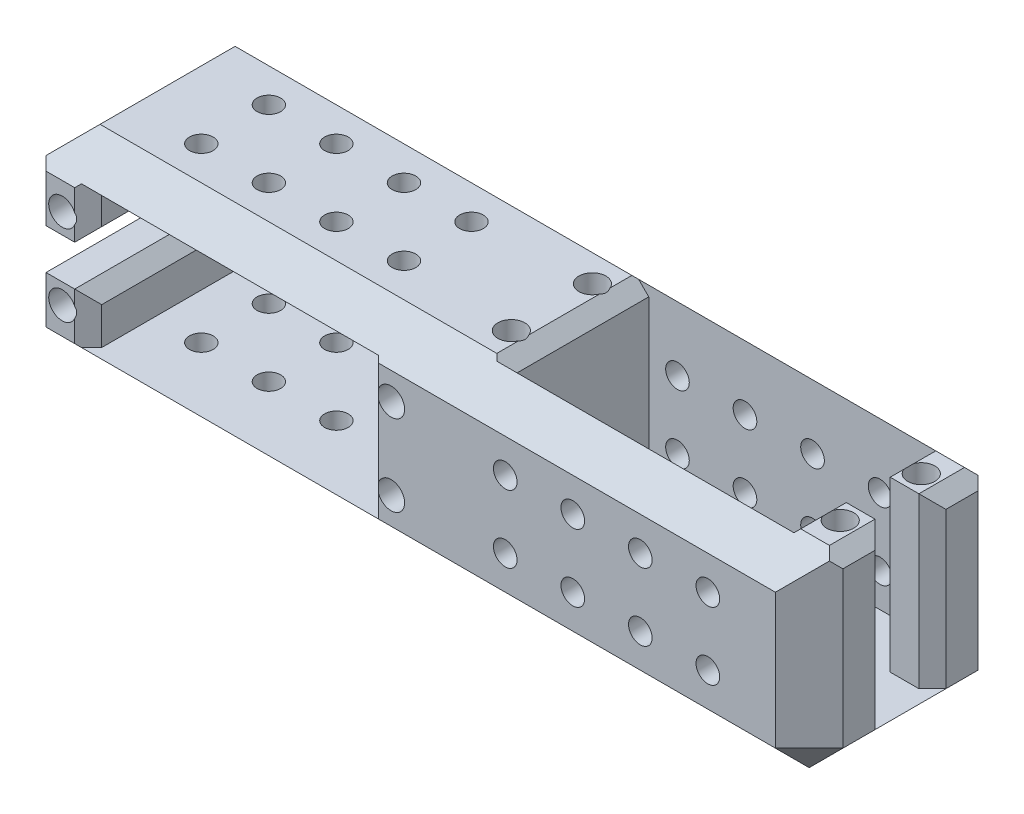
SolidWorks part; units mm, degrees
ref_plane "前视基准面" through (0, 0, 0) normal (0, 0, 1) x (1, 0, 0)
ref_plane "上视基准面" through (0, 0, 0) normal (0, 1, 0) x (1, 0, 0)
ref_plane "右视基准面" through (0, 0, 0) normal (1, 0, 0) x (0, 0, -1)
other "Configuration Table"
sketch "Sketch1" plane through (0, 0, 0) normal (0, 0, 1) x (1, 0, 0)
  line L1 (-28.75, -15) -> (28.75, -15)
  line L2 (-28.75, -15) -> (-28.75, 15)
  line L3 (-28.75, 15) -> (28.75, 15)
  line L4 (28.75, -15) -> (28.75, 15)
  line L5 (-28.75, -15) -> (28.75, 15) construction
  line L6 (-28.75, 15) -> (28.75, -15) construction
  point P0 (0, 0)
  dimension "D1" = 57.5
  dimension "D2" = 30
extrude "Boss-Extrude1" add sketch "Sketch1" along normal blind 30
sketch "Sketch2" plane through (0, 0, 30) normal (0, 0, 1) x (1, 0, 0)
  line L1 (-20.5, -10.5) -> (20.5, -10.5)
  line L2 (-20.5, -10.5) -> (-20.5, 10.5)
  line L3 (-20.5, 10.5) -> (20.5, 10.5)
  line L4 (20.5, -10.5) -> (20.5, 10.5)
  line L5 (-20.5, -10.5) -> (20.5, 10.5) construction
  line L6 (-20.5, 10.5) -> (20.5, -10.5) construction
  point P0 (0, 0)
  dimension "D1" = 41
  dimension "D2" = 21
extrude "Cut-Extrude1" cut sketch "Sketch2" against normal blind 25
ref_plane "Plane1" through (0, 0, 15) normal (0, 0, 1) x (1, 0, 0)
sketch "Sketch8" plane through (0, 0, 30) normal (0, 0, 1) x (1, 0, 0)
  line L0 (0, 0) -> (24.35, 0) construction
  line L1 (24.35, 0) -> (24.35, 6) construction
  line L2 (0, 0) -> (0, 15) construction
  line L3 (28.75, 15) -> (-28.75, 15) construction
  circle A0 centre (24.35, 6) radius 2
  circle A4 centre (24.35, -6) radius 2
  circle A5 centre (-24.35, -6) radius 2
  circle A6 centre (-24.35, 6) radius 2
  dimension "D3" = 4
  dimension "D1" = 6
  dimension "D2" = 24.35
extrude "Cut-Extrude6" cut sketch "Sketch8" against normal blind 10
sketch "Sketch9" plane through (0, 0, 30) normal (0, 0, 1) x (1, 0, 0)
  line L0 (-20.5, 0) -> (-28.75, 0) construction
  line L1 (-20.5, 10.5) -> (-20.5, -10.5) construction
  line L2 (-28.75, 15) -> (-28.75, -15) construction
  line L3 (-28.75, 0) -> (-24.625, 0) construction
  line L5 (-28.75, -3) -> (-20.5, -3)
  line L6 (-28.75, -3) -> (-28.75, 3)
  line L7 (-28.75, 3) -> (-20.5, 3)
  line L8 (-20.5, -3) -> (-20.5, 3)
  line L9 (-28.75, -3) -> (-20.5, 3) construction
  line L10 (-28.75, 3) -> (-20.5, -3) construction
  dimension "D1" = 6
extrude "Cut-Extrude7" cut sketch "Sketch9" against normal blind 25
sketch "Sketch10" plane through (0, 0, 5) normal (0, 0, 1) x (1, 0, 0)
  line L0 (0, 0) -> (-10, 0) construction
  circle A0 centre (-10, 0) radius 5
  dimension "D2" = 10
  dimension "D1" = 10
extrude "Cut-Extrude8" cut sketch "Sketch10" against normal blind 10
sketch "Sketch11" plane through (28.75, 0, 0) normal (1, 0, 0) x (0, 0, -1)
  line L0 (-30, 0) -> (0, 0) construction
  line L1 (-30, -15) -> (-30, 15) construction
  line L2 (0, 0) -> (-15, 0) construction
  line L4 (-30, -15) -> (0, -15)
  line L5 (-30, -15) -> (-30, 15)
  line L6 (-30, 15) -> (0, 15)
  line L7 (0, -15) -> (0, 15)
  line L8 (-30, -15) -> (0, 15) construction
  line L9 (-30, 15) -> (0, -15) construction
  dimension "D1" = 30
  dimension "D2" = 30
extrude "Boss-Extrude2" add sketch "Sketch11" along normal blind 57.5
sketch "Sketch14" plane through (0, 15, 0) normal (0, 1, 0) x (1, 0, 0)
  line L0 (28.75, 0) -> (28.75, -30) construction
  line L1 (86.25, 0) -> (-28.75, 0) construction
  line L2 (86.25, -30) -> (-28.75, -30) construction
  line L4 (28.75, -15) -> (86.25, -15) construction
  line L7 (86.25, 0) -> (86.25, -30) construction
  line L8 (86.25, -15) -> (57.5, -15) construction
  line L9 (57.5, -15) -> (81.85, -15) construction
  line L14 (81.85, -15) -> (81.85, -9) construction
  line L15 (57.5, -15) -> (57.5, -24.9554) construction
  circle A4 centre (81.85, -9) radius 2
  circle A5 centre (81.85, -21) radius 2
  circle A6 centre (33.15, -21) radius 2
  circle A7 centre (33.15, -9) radius 2
  dimension "D3" = 24.35
  dimension "D1" = 4
  dimension "D2" = 6
extrude "Cut-Extrude14" cut sketch "Sketch14" against normal blind 15
sketch "Sketch18" plane through (0, 15, 0) normal (0, 1, 0) x (1, 0, 0)
  line L0 (28.75, 0) -> (28.75, -30) construction
  line L1 (86.25, 0) -> (-28.75, 0) construction
  line L2 (86.25, -30) -> (-28.75, -30) construction
  line L3 (28.75, -30) -> (28.75, -15) construction
  line L4 (28.75, -15) -> (86.25, -15) construction
  line L5 (86.25, 0) -> (86.25, -30) construction
  line L6 (86.25, -15) -> (57.5, -15) construction
  line L7 (78, -15) -> (86.25, -15) construction
  line L8 (37, -25.5) -> (78, -25.5)
  line L9 (37, -25.5) -> (37, -4.5)
  line L10 (37, -4.5) -> (78, -4.5)
  line L11 (78, -25.5) -> (78, -4.5)
  line L12 (37, -25.5) -> (78, -4.5) construction
  line L13 (37, -4.5) -> (78, -25.5) construction
  line L14 (86.25, -15) -> (82.125, -15) construction
  line L16 (78, -18.25) -> (86.25, -18.25)
  line L17 (78, -18.25) -> (78, -11.75)
  line L18 (78, -11.75) -> (86.25, -11.75)
  line L19 (86.25, -18.25) -> (86.25, -11.75)
  line L20 (78, -18.25) -> (86.25, -11.75) construction
  line L21 (78, -11.75) -> (86.25, -18.25) construction
  line M14 (86.25, -30) -> (86.25, 0)
  dimension "D1" = 41
  dimension "D2" = 21
  dimension "D3" = 6.5
extrude "Cut-Extrude15" cut sketch "Sketch18" against normal blind 25 contours L8 L11 L10 L9 | L18 L11 L16 M14 region at (57.5, 15, 15) region at (82.125, 15, 15)
sketch "Sketch19" plane through (0, -15, 0) normal (0, -1, 0) x (1, 0, 0)
  line L0 (28.75, 30) -> (28.75, 0) construction
  line L1 (-28.75, 30) -> (86.25, 30) construction
  line L2 (-28.75, 0) -> (86.25, 0) construction
  line L3 (28.75, 0) -> (28.75, 15) construction
  line L4 (28.75, 15) -> (86.25, 15) construction
  line L5 (16.5, 15) -> (-16.5, 15) construction
  line L6 (86.25, 15) -> (57.5, 15) construction
  line L7 (57.5, 15) -> (67.5, 15) construction
  circle A0 centre (67.5, 15) radius 5
  dimension "D2" = 10
  dimension "D1" = 10
  dimension "D3" = 28.75
extrude "Cut-Extrude16" cut sketch "Sketch19" against normal blind 25
chamfer "Chamfer4" distance 5 angle 45 10 edges at (28.75, -15, 0) (28.75, -15, 30) (28.75, 15, 30) (86.25, 0, 30) (86.25, -15, 15) (86.25, 0, 0) (28.75, 15, 0) (-28.75, 15, 15) (-28.75, 0, 0) (-28.75, -15, 15)
chamfer "Chamfer5" distance 2 angle 45 18 edges at (78, 15, 8.375) (78, 2.5, 11.75) (86.25, 15, 8.375) (86.25, 2.5, 11.75) (78, 15, 21.625) (78, 2.5, 18.25) (86.25, 15, 21.625) (86.25, 2.5, 18.25) (-28.75, -6.5, 30) (-28.75, -3, 17.5) (-20.5, -6.5, 30) (-20.5, -3, 17.5) (-28.75, 6.5, 30) (-28.75, 3, 17.5) (-20.5, 6.5, 30) (-20.5, 3, 17.5) (20.5, 0, 30) (37, 15, 15)
sketch "Sketch23" plane through (0, 0, 30) normal (0, 0, 1) x (1, 0, 0)
  line L0 (81.25, 0) -> (71.25, 0) construction
  line L1 (81.25, -10) -> (81.25, 10) construction
  line L2 (71.25, 0) -> (71.25, 5) construction
  circle A0 centre (71.25, 5) radius 1.75
  circle A1 centre (71.25, -5) radius 1.75
  circle A2 centre (61.25, 5) radius 1.75
  circle A3 centre (61.25, -5) radius 1.75
  circle A4 centre (51.25, 5) radius 1.75
  circle A5 centre (51.25, -5) radius 1.75
  circle A6 centre (41.25, 5) radius 1.75
  circle A7 centre (41.25, -5) radius 1.75
  circle A10 centre (31.25, 5) radius 1.75 [skipped]
  circle A11 centre (31.25, -5) radius 1.75 [skipped]
  dimension "D1" = 3.5
  dimension "D2" = 5
  dimension "D3" = 10
  dimension "D5" = 10
  dimension "D4" = 5
extrude "Cut-Extrude19" cut sketch "Sketch23" against normal through all
sketch "Sketch24" plane through (0, 15, 0) normal (0, 1, 0) x (1, 0, 0)
  line L2 (-23.75, -15) -> (-13.75, -15) construction
  line L3 (-23.75, -5) -> (-23.75, -25) construction
  line L4 (-16.5, -15) -> (16.5, -15) construction
  line L5 (-13.75, -15) -> (-13.75, -10) construction
  line L6 (-3.75, -15) -> (-3.75, -10) construction
  line L7 (6.25, -15) -> (6.25, -10) construction
  line L8 (16.25, -15) -> (16.25, -10) construction
  circle A8 centre (-13.75, -10) radius 1.75
  circle A9 centre (-13.75, -20) radius 1.75
  circle A10 centre (-3.75, -10) radius 1.75
  circle A11 centre (-3.75, -20) radius 1.75
  circle A12 centre (6.25, -10) radius 1.75
  circle A13 centre (6.25, -20) radius 1.75
  circle A14 centre (16.25, -10) radius 1.75
  circle A15 centre (16.25, -20) radius 1.75
  dimension "D1" = 10
  dimension "D5" = 3.5
  dimension "D6" = 5
  dimension "D7" = 10
  dimension "D8" = 4
extrude "Cut-Extrude20" cut sketch "Sketch24" against normal through all
sketch "Sketch26" plane through (0, 0, 5) normal (0, 0, 1) x (1, 0, 0)
  circle A0 centre (-10, 0) radius 7.5
  dimension "D1" = 15
extrude "Cut-Extrude21" cut sketch "Sketch26" against normal blind 2.5
sketch "Sketch27" plane through (0, -10, 0) normal (0, 1, 0) x (1, 0, 0)
  circle A0 centre (67.5, -15) radius 7.5
  dimension "D1" = 15
extrude "Cut-Extrude22" cut sketch "Sketch27" against normal blind 2.5
